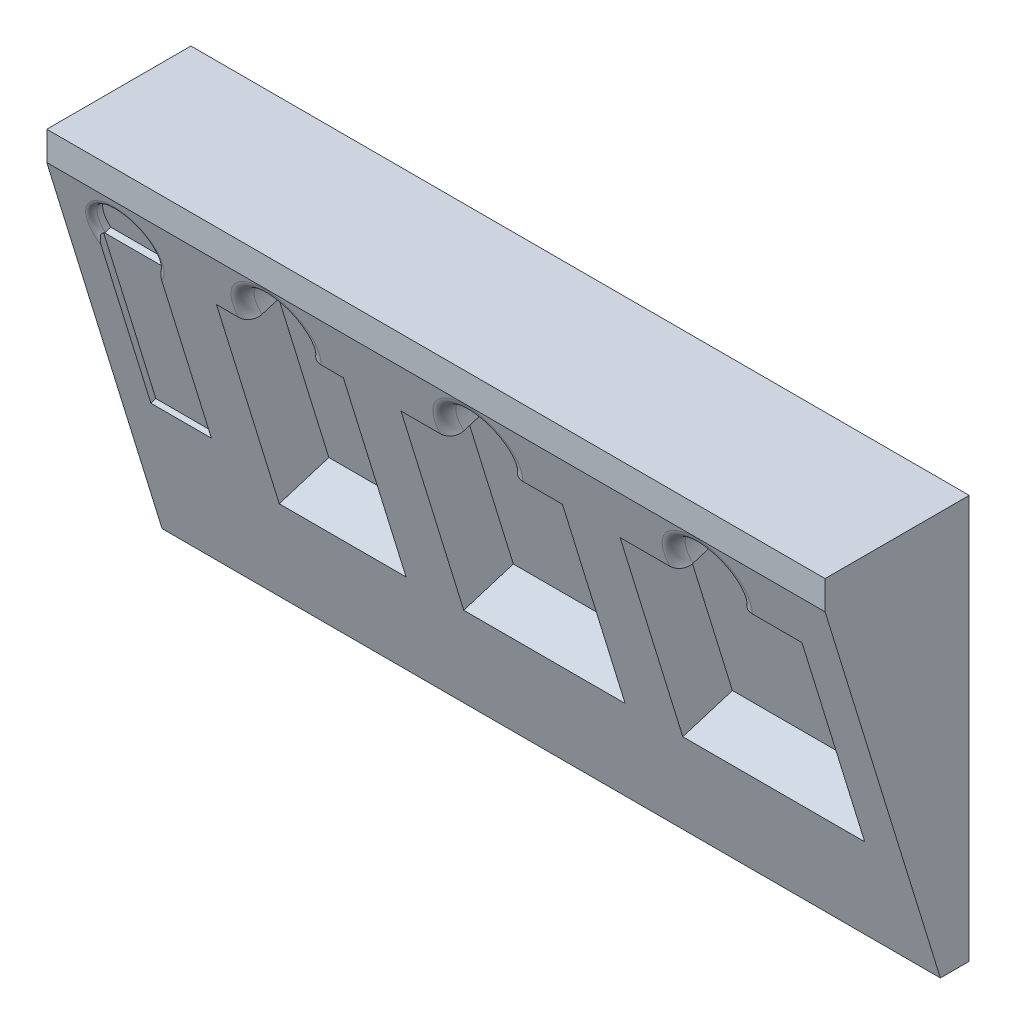
SolidWorks part; units mm, degrees
ref_plane "Top" through (0, 0, 0) normal (0, 0, 1) x (1, 0, 0)
ref_plane "Front" through (0, 0, 0) normal (0, 1, 0) x (1, 0, 0)
ref_plane "Right" through (0, 0, 0) normal (1, 0, 0) x (0, 0, -1)
sketch "Sketch1" plane through (0, 0, 0) normal (0, 0, 1) x (1, 0, 0)
  line L1 (-67.5, -35) -> (67.5, -35)
  line L2 (-67.5, -35) -> (-67.5, 35)
  line L3 (-67.5, 35) -> (67.5, 35)
  line L4 (67.5, -35) -> (67.5, 35)
  line L5 (-67.5, -35) -> (67.5, 35) construction
  line L6 (-67.5, 35) -> (67.5, -35) construction
  point P0 (0, 0)
  dimension "D1" = 70
  dimension "D2" = 135
extrude "Boss-Extrude1" add sketch "Sketch1" along normal blind 25
sketch "Sketch2" plane through (-67.5, 0, 0) normal (-1, 0, 0) x (0, 0, 1)
  line L0 (25, 30) -> (5, -35)
  line L1 (25, 35) -> (25, -35) construction
  line L2 (25, -35) -> (0, -35) construction
  line L3 (25, 35) -> (0, 35) construction
  line L4 (0, 35) -> (0, -35) construction
  line L5 (25, 30) -> (31.5353, -44.5522)
  line L6 (31.5353, -44.5522) -> (5, -35)
  dimension "D1" = 5
  dimension "D2" = 5
extrude "Cut-Extrude1" cut sketch "Sketch2" against normal through all both and the other way through all
sketch "Sketch3" plane through (0, -4.4324, 14.4054) normal (0, -0.2941, 0.9558) x (1, 0, 0)
  line L0 (-67.5, 26.0255) -> (67.5, 26.0255) construction
  line L1 (-67.5, -31.9818) -> (-67.5, 36.0255) construction
  line L2 (67.5, 36.0255) -> (67.5, -31.9818) construction
  line L3 (67.5, 36.0255) -> (-67.5, 36.0255) construction
  line L5 (-61.5, 26.0255) -> (-51, 26.0255)
  line L6 (-61.5, 26.0255) -> (-61.5, -4.9745)
  line L7 (-61.5, -4.9745) -> (-51, -4.9745)
  line L8 (-51, 26.0255) -> (-51, -4.9745)
  line L9 (-41, 26.0255) -> (-19, 26.0255)
  line L10 (-41, 26.0255) -> (-41, -10.9745)
  line L11 (-41, -10.9745) -> (-19, -10.9745)
  line L12 (-19, 26.0255) -> (-19, -10.9745)
  line L13 (-9, 26.0255) -> (19, 26.0255)
  line L14 (-9, 26.0255) -> (-9, -10.9745)
  line L15 (-9, -10.9745) -> (19, -10.9745)
  line L16 (19, 26.0255) -> (19, -10.9745)
  line L17 (29, 26.0255) -> (60.55, 26.0255)
  line L18 (29, 26.0255) -> (29, -10.9745)
  line L19 (29, -10.9745) -> (60.55, -10.9745)
  line L20 (60.55, 26.0255) -> (60.55, -10.9745)
  dimension "D1" = 10
  dimension "D2" = 10.5
  dimension "D3" = 31
  dimension "D4" = 22
  dimension "D5" = 37
  dimension "D6" = 10
  dimension "D7" = 10
  dimension "D8" = 28
  dimension "D9" = 37
  dimension "D10" = 37
  dimension "D11" = 31.55
  dimension "D12" = 10
  dimension "D13" = 6
extrude "Cut-Extrude4" cut sketch "Sketch3" against normal blind 9
sketch "Sketch4" plane through (0, -1.7857, 5.8034) normal (0, -0.2941, 0.9558) x (1, 0, 0)
  line L0 (-51, 26.0255) -> (-61.5, 26.0255) construction
  line L1 (-63.8906, 27.4271) -> (-48.2695, 27.4271)
  line L2 (-63.8906, 27.4271) -> (-63.8906, -7.0957)
  line L3 (-63.8906, -7.0957) -> (-48.2695, -7.0957)
  line L4 (-48.2695, 27.4271) -> (-48.2695, -7.0957)
  line L5 (-51, -4.9745) -> (-51, 26.0255) construction
  line L6 (-61.5, -4.9745) -> (-51, -4.9745) construction
  line L8 (-61.5, 26.0255) -> (-61.5, -4.9745) construction
extrude "Boss-Extrude2" add sketch "Sketch4" along normal blind 8.1
sketch "Sketch5" plane through (0, -4.4324, 14.4054) normal (0, -0.2941, 0.9558) x (1, 0, 0)
  line L0 (-19, 26.0255) -> (-41, 26.0255) construction
  line L1 (-35, 26.0255) -> (-25, 26.0255)
  line L2 (0, 26.0255) -> (10, 26.0255)
  line L3 (39.775, 26.0255) -> (49.775, 26.0255)
  line L5 (-30, -10.9745) -> (-30, 67.6081) construction
  line L6 (-41, -10.9745) -> (-19, -10.9745) construction
  line L7 (5, -10.9745) -> (5, 67.6081) construction
  line L8 (-9, -10.9745) -> (19, -10.9745) construction
  line L9 (44.775, -10.9745) -> (44.775, 67.6081) construction
  line L10 (29, -10.9745) -> (60.55, -10.9745) construction
  arc A0 (-35, 26.0255) -> (-25, 26.0255) centre (-30, 28.3168) cw
  arc A1 (0, 26.0255) -> (10, 26.0255) centre (5, 28.3168) cw
  arc A2 (39.775, 26.0255) -> (49.775, 26.0255) centre (44.775, 28.3168) cw
  point P23 (0, 0)
  point P24 (0, 0)
  dimension "D2" = 5.5
  dimension "D1" = 10
extrude "Cut-Extrude5" cut sketch "Sketch5" against normal blind 10
sketch "Sketch6" plane through (0, -4.4324, 14.4054) normal (0, -0.2941, 0.9558) x (1, 0, 0)
  line L0 (-61.2866, 25.9482) -> (-51.2134, 25.9482)
  line L1 (-56.25, -4.9745) -> (-56.25, 47.5105) construction
  line L2 (-61.5, -4.9745) -> (-51, -4.9745) construction
  arc A0 (-61.2866, 25.9482) -> (-51.2134, 25.9482) centre (-56.25, 28.2395) cw
  point P3 (-56.25, 28.4491)
  point P8 (-56.25, 28.3087)
  point P9 (-56.25, 28.2395)
extrude "Cut-Extrude6" cut sketch "Sketch6" against normal blind 2
sketch "Sketch7" plane through (0, -4.4324, 14.4054) normal (0, -0.2941, 0.9558) x (1, 0, 0)
  line L0 (-56.25, -4.9745) -> (-56.25, 55.1735) construction
  line L1 (-51, -4.9745) -> (-61.5, -4.9745) construction
  line L2 (-30, -10.9745) -> (-30, 55.1735) construction
  line L3 (-41, -10.9745) -> (-19, -10.9745) construction
  line L4 (5, -10.9745) -> (5, 55.1735) construction
  line L5 (-9, -10.9745) -> (19, -10.9745) construction
  line L6 (44.775, -10.9745) -> (44.775, 55.1735) construction
  line L7 (29, -10.9745) -> (60.55, -10.9745) construction
  line L8 (-61.5, -20.0423) -> (-51, -20.0423) construction
  line L9 (-41, -20.0423) -> (-19, -20.0423) construction
  line L10 (-9, -20.0423) -> (19, -20.0423) construction
  line L11 (29, -20.0423) -> (60.55, -20.0423) construction
  line L12 (-61.5, -4.9745) -> (-61.5, 26.0255) construction
  line L13 (-51, -4.9745) -> (-51, 26.0255) construction
  line L14 (-41, 26.0255) -> (-41, -10.9745) construction
  line L15 (-19, -10.9745) -> (-19, 26.0255) construction
  line L16 (-9, 26.0255) -> (-9, -10.9745) construction
  line L17 (19, -10.9745) -> (19, 26.0255) construction
  line L18 (29, 26.0255) -> (29, -10.9745) construction
  line L19 (60.55, -10.9745) -> (60.55, 26.0255) construction
  line L20 (-41, -10.9745) -> (-19, -10.9745) construction
  line L21 (29, -10.9745) -> (60.55, -10.9745) construction
  text T0 "1" font "Arial Rounded MT Bold" height 6.35
  text T1 "20" font "Arial Rounded MT Bold" height 6.35
  text T2 "25" font "Arial Rounded MT Bold" height 6.35
  text T3 "30" font "Arial Rounded MT Bold" height 6.35
  point P26 (0, 0)
extrude "Cut-Extrude7" [suppressed] cut sketch "Sketch7" against normal blind 3
fillet "Fillet1" radius 2 3 edges at (44.775, 27.889, 24.3504) (5, 27.889, 24.3504) (-30, 27.889, 24.3504)
fillet "Fillet2" radius 1 1 edges at (-56.25, 27.8469, 24.3375)
shell "Shell3" thickness 1 removed face at (0, 0, 0)
